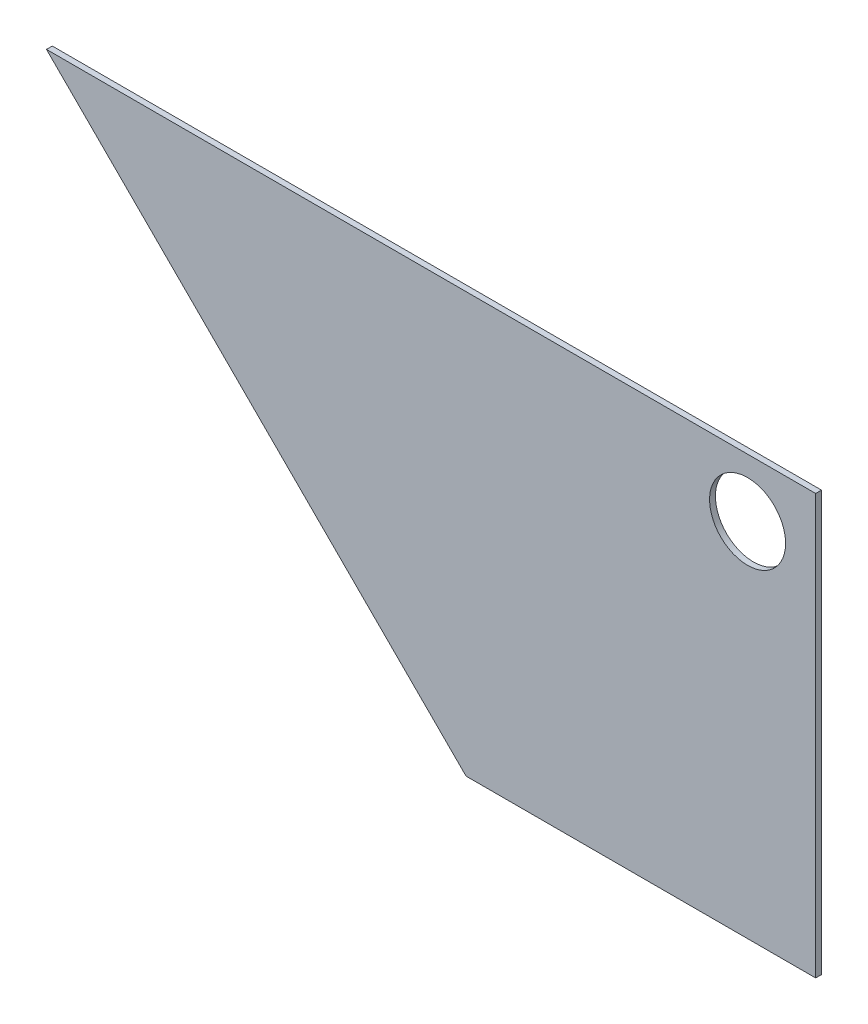
SolidWorks part; units mm, degrees
ref_plane "Front Plane" through (0, 0, 0) normal (0, 0, 1) x (1, 0, 0)
ref_plane "Top Plane" through (0, 0, 0) normal (0, 1, 0) x (1, 0, 0)
ref_plane "Right Plane" through (0, 0, 0) normal (1, 0, 0) x (0, 0, -1)
sketch "Sketch1" plane through (0, 0, 0) normal (0, 0, 1) x (1, 0, 0)
  line L0 (-196.3894, 107.1215) -> (32.2106, -121.4785)
  line L1 (32.2106, -121.4785) -> (222.7106, -121.4785)
  line L3 (-196.3894, 107.1215) -> (222.7106, 107.1215)
  line L4 (222.7106, -121.4785) -> (222.7106, 107.1215)
  line L6 (-196.3894, 107.1215) -> (222.7106, -121.4785) construction
  point P0 (0, 0)
  dimension "D1" = 45
  dimension "D2" = 228.6
  dimension "D3" = 419.1
extrude "Boss-Extrude1" add sketch "Sketch1" along normal blind 3.175
sketch "Sketch3" plane through (0, 0, 3.175) normal (0, 0, 1) x (1, 0, 0)
  line L0 (-196.3894, 107.1215) -> (32.2106, -121.4785) construction
  line L3 (32.2106, -121.4785) -> (222.7106, -121.4785) construction
  circle A0 centre (185.5906, 75.3715) radius 20.701
  dimension "D1" = 247.65
  dimension "D2" = 196.85
extrude "Cut-Extrude2" cut sketch "Sketch3" against normal through all
